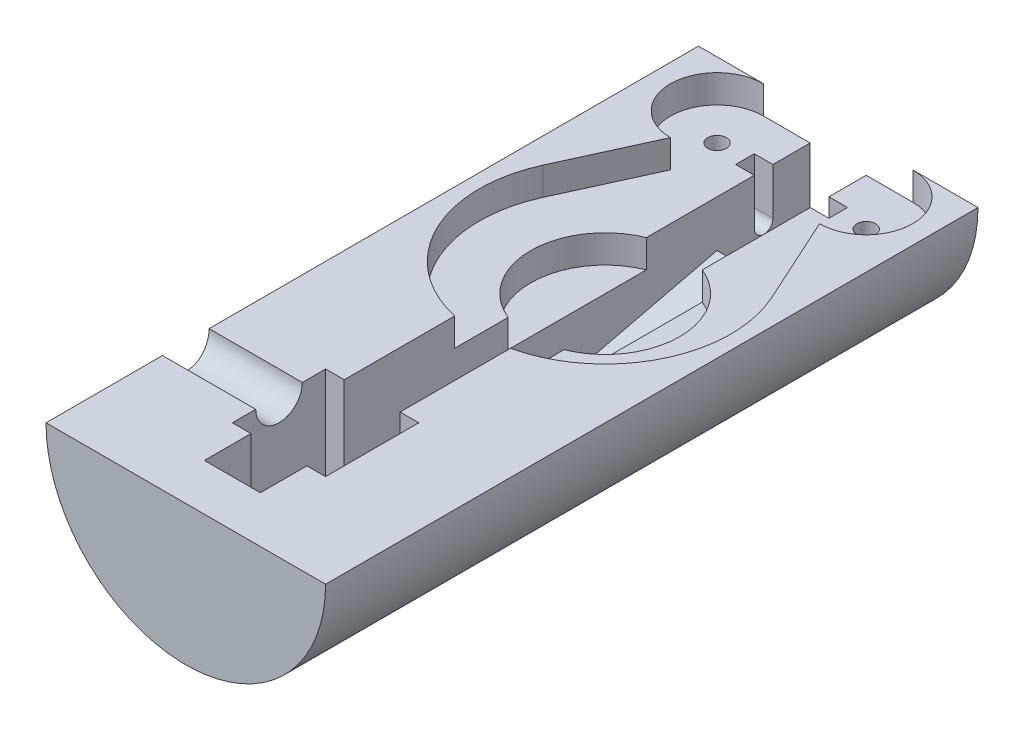
SolidWorks part; units mm, degrees
ref_plane "Alzado" through (0, 0, 0) normal (0, 0, 1) x (1, 0, 0)
ref_plane "Planta" through (0, 0, 0) normal (0, 1, 0) x (1, 0, 0)
ref_plane "Vista lateral" through (0, 0, 0) normal (1, 0, 0) x (0, 0, -1)
sketch "Croquis1" plane through (0, 0, 0) normal (0, 0, 1) x (1, 0, 0)
  line L0 (-15, 0) -> (15, 0)
  arc A1 (-15, 0) -> (15, 0) centre (0, 0) ccw
  dimension "D2" = 15
extrude "Saliente-Extruir1" add sketch "Croquis1" along normal blind 35 and the other way blind 35
sketch "Croquis3" plane through (0, 0, 0) normal (0, 1, 0) x (1, 0, 0)
  line L0 (0, 0) -> (0, 30) construction
  line L1 (-8, 25) -> (-12.2845, 15.5983)
  line L2 (0, 30) -> (0, 10) construction
  line L3 (8, 25) -> (12.2845, 15.5983)
  line L4 (-8, 35) -> (8, 35)
  line L8 (0, 30) -> (8, 30) construction
  line L9 (0, 30) -> (-8, 30) construction
  arc A0 (-8, 35) -> (-8, 25) centre (-8, 30) ccw
  arc A1 (8, 25) -> (8, 35) centre (8, 30) ccw
  arc A5 (-12.2845, 15.5983) -> (12.2845, 15.5983) centre (0, 10) ccw
  dimension "D6" = 10
  dimension "D8" = 27
  dimension "D1" = 30
  dimension "D2" = 20
  dimension "D4" = 8
  dimension "D5" = 8
extrude "Cortar-Extruir1" cut sketch "Croquis3" against normal blind 3
sketch "Croquis4" plane through (0, -3, 0) normal (0, 1, 0) x (1, 0, 0)
  circle A0 centre (0, 10) radius 8
  dimension "D1" = 16
extrude "Cortar-Extruir2" cut sketch "Croquis4" against normal blind 3
sketch "Croquis5" plane through (0, -6, 0) normal (0, 1, 0) x (1, 0, 0)
  circle A0 centre (0, 10) radius 2.5
  dimension "D1" = 5
extrude "Cortar-Extruir3" cut sketch "Croquis5" against normal blind 10
sketch "Croquis6" plane through (0, -3, 0) normal (0, 1, 0) x (1, 0, 0)
  line L0 (8, 35) -> (-8, 35) construction
  line L1 (-3, 25) -> (3, 25)
  line L2 (-3, 25) -> (-3, 35)
  line L3 (-3, 35) -> (3, 35)
  line L4 (3, 25) -> (3, 35)
  line L5 (-3, 25) -> (3, 35) construction
  line L6 (-3, 35) -> (3, 25) construction
  circle A0 centre (-8, 30) radius 1.5
  circle A1 centre (8, 30) radius 1.5
  point P6 (0, 30)
  dimension "D1" = 3
  dimension "D2" = 10
  dimension "D3" = 8
  dimension "D4" = 6
  dimension "D5" = 5
extrude "Cortar-Extruir5" cut sketch "Croquis6" against normal blind 10 contours L2 L3 L4 L1
sketch "Croquis7" plane through (0, -3, 0) normal (0, 1, 0) x (1, 0, 0)
  line L0 (-3, 30) -> (-5, 30) construction
  line L1 (-3, 25) -> (-3, 35) construction
  line L2 (3, 30) -> (5, 30) construction
  line L3 (3, 25) -> (3, 35) construction
  line L5 (-5, 31) -> (-3, 31)
  line L6 (-5, 31) -> (-5, 29)
  line L7 (-5, 29) -> (-3, 29)
  line L8 (-3, 31) -> (-3, 29)
  line L9 (-5, 31) -> (-3, 29) construction
  line L10 (-5, 29) -> (-3, 31) construction
  line L11 (3, 31) -> (5, 31)
  line L12 (3, 31) -> (3, 29)
  line L13 (3, 29) -> (5, 29)
  line L14 (5, 31) -> (5, 29)
  line L15 (3, 31) -> (5, 29) construction
  line L16 (3, 29) -> (5, 31) construction
  point P8 (-4, 30)
  point P13 (4, 30)
  dimension "D1" = 2
  dimension "D2" = 2
  dimension "D3" = 2
  dimension "D4" = 2
extrude "Cortar-Extruir6" cut sketch "Croquis7" against normal blind 5
sketch "Croquis8" plane through (0, -3, 0) normal (0, 1, 0) x (1, 0, 0)
  circle A0 centre (-8, 30) radius 1
  circle A1 centre (8, 30) radius 1
  dimension "D1" = 2
extrude "Cortar-Extruir7" cut sketch "Croquis8" against normal blind 2
sketch "Croquis9" plane through (0, -3, 0) normal (0, 1, 0) x (1, 0, 0)
  line L0 (0, 30) -> (0, 0) construction
  line L1 (15, 35) -> (-15, 35) construction
  line L3 (-3, 5) -> (3, 5)
  line L4 (-3, 5) -> (-3, -5)
  line L5 (-3, -5) -> (3, -5)
  line L6 (3, 5) -> (3, -5)
  line L7 (-3, 5) -> (3, -5) construction
  line L8 (-3, -5) -> (3, 5) construction
  point P3 (0, 35)
  dimension "D1" = 30
  dimension "D2" = 5
  dimension "D4" = 10
extrude "Cortar-Extruir8" cut sketch "Croquis9" against normal blind 12
sketch "Croquis10" plane through (0, 0, 0) normal (1, 0, 0) x (0, 0, -1)
  line L0 (29, -8) -> (31, -8) construction
  circle A0 centre (30, -8) radius 1
extrude "Cortar-Extruir9" cut sketch "Croquis10" against normal blind 5 and the other way blind 5
sketch "Croquis11" plane through (0, 0, 0) normal (1, 0, 0) x (0, 0, -1)
  line L0 (0, 0) -> (0, -12.5) construction
  line L1 (-6, -15) -> (6, -15)
  line L2 (1, -14) -> (6, -14)
  line L3 (-1, -14) -> (-1, -8)
  line L4 (-6, -14) -> (-1, -14)
  line L5 (1, -14) -> (1, -8)
  line L6 (30, -8) -> (-11.3011, -8) construction
  line L8 (-6, -14) -> (-6, -15)
  line L10 (6, -14) -> (6, -15)
  arc A0 (1, -8) -> (-1, -8) centre (0, -8) ccw
  point P8 (0, -15)
  dimension "D2" = 1
  dimension "D1" = 12.5
  dimension "D3" = 6
  dimension "D4" = 8
  dimension "D5" = 14
extrude "Cortar-Extruir10" cut sketch "Croquis11" against normal blind 5 and the other way blind 5
sketch "Croquis12" plane through (0, 0, 0) normal (1, 0, 0) x (0, 0, -1)
  line L0 (-20, -8) -> (-20, 0) construction
  line L1 (-3, -13) -> (-21.6588, -9.8615)
  line L2 (25, -8) -> (25, -3)
  line L3 (25, -3) -> (4, -3)
  line L4 (4, -13) -> (4, -3)
  line L5 (4, -13) -> (25, -8)
  line L6 (-3, 0) -> (-30, 0)
  line L7 (-3, 0) -> (-3, -13)
  line L8 (-3, -13) -> (-30, -13) construction
  line L9 (-30, 0) -> (-30, -13) construction
  line L10 (0, -8) -> (-20, -8) construction
  arc A0 (-30, 0) -> (-21.6588, -9.8615) centre (-20, 0) ccw
  dimension "D1" = 13
  dimension "D2" = 27
  dimension "D3" = 20
  dimension "D4" = 7
  dimension "D5" = 21
  dimension "D6" = 4
extrude "Cortar-Extruir11" cut sketch "Croquis12" against normal blind 3 and the other way blind 3
sketch "Croquis14" plane through (0, 0, 0) normal (0, 1, 0) x (1, 0, 0)
  line L0 (0, 10) -> (0, -20) construction
  line L1 (0, -3) -> (0, -30) construction
  line L3 (0, -20) -> (3, -20) construction
  line L4 (3, -21.6588) -> (3, -5) construction
  line L5 (3, -20) -> (3, -15) construction
  line L6 (3, -3.1624) -> (3, -30) construction
  line L7 (-3, -3.1624) -> (-3, -30) construction
  line L8 (3, -15) -> (5, -15)
  line L9 (3, -15) -> (3, -25)
  line L10 (3, -25) -> (5, -25)
  line L11 (5, -15) -> (5, -25)
  line L12 (-3, -15) -> (-5, -15)
  line L13 (-3, -15) -> (-3, -25)
  line L14 (-3, -25) -> (-5, -25)
  line L15 (-5, -15) -> (-5, -25)
  dimension "D1" = 30
  dimension "D2" = 5
  dimension "D3" = 10
  dimension "D4" = 10
  dimension "D5" = 5
  dimension "D6" = 2
  dimension "D7" = 2
sketch "Croquis15" plane through (0, 0, 0) normal (1, 0, 0) x (0, 0, -1)
  circle A0 centre (-20, 0) radius 2.5
  dimension "D1" = 5
extrude "Cortar-Extruir12" cut sketch "Croquis15" against normal blind 15
extrude "Cortar-Extruir13" cut sketch "Croquis14" against normal blind 10
